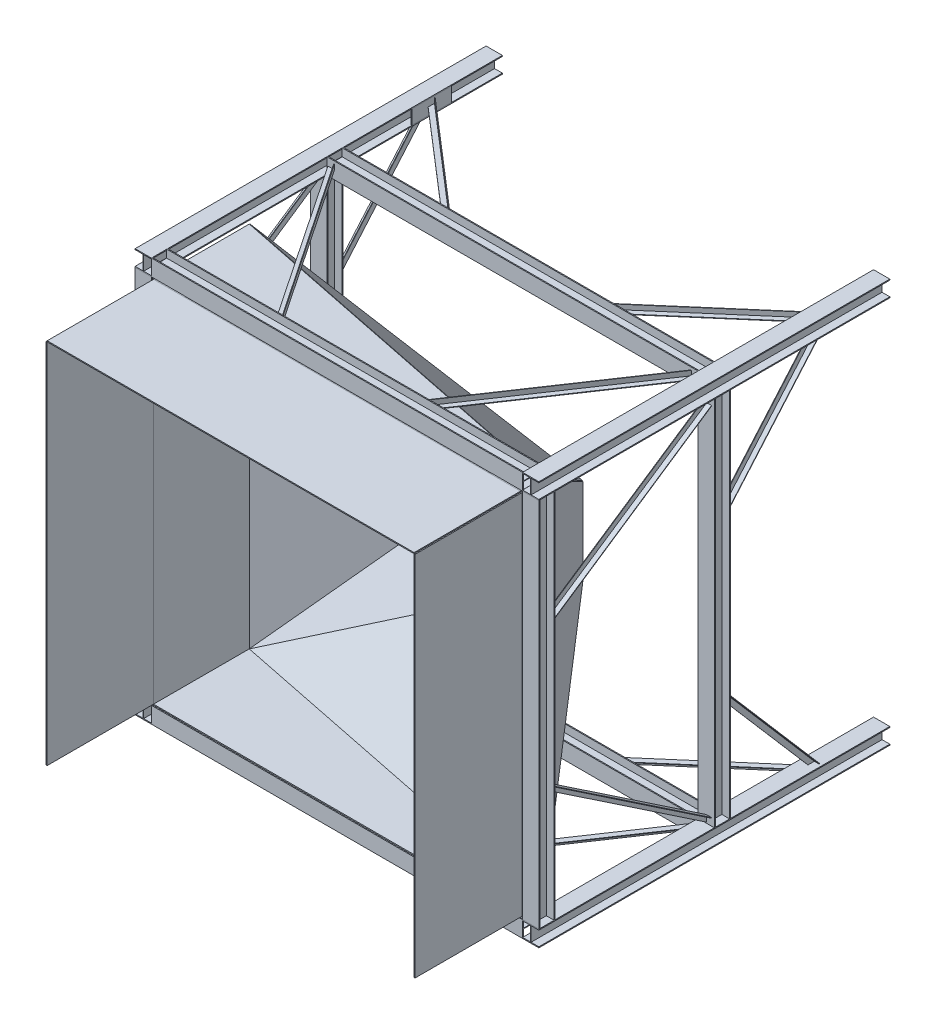
SolidWorks part; units mm, degrees
other "DetailItem1"
other "DetailItem2"
other "DetailItem3"
other "DetailItem4"
other "DetailItem5"
other "DetailItem6"
other "DetailItem7"
other "DetailItem8"
other "DetailItem9"
other "DetailItem10"
other "DetailItem11"
other "DetailItem12"
other "DetailItem13"
other "DetailItem14"
other "DetailItem15"
other "DetailItem16"
other "DetailItem17"
other "DetailItem18"
other "DetailItem19"
other "DetailItem20"
other "DetailItem21"
other "DetailItem22"
other "DetailItem23"
other "DetailItem24"
other "DetailItem25"
other "DetailItem26"
other "DetailItem27"
other "DetailItem28"
other "DetailItem29"
other "DetailItem30"
other "DetailItem31"
other "DetailItem32"
other "DetailItem33"
other "DetailItem34"
other "DetailItem35"
other "DetailItem36"
other "DetailItem37"
other "DetailItem38"
other "DetailItem39"
other "DetailItem40"
other "DetailItem41"
other "DetailItem42"
other "DetailItem43"
other "DetailItem44"
other "DetailItem45"
other "DetailItem46"
other "DetailItem47"
other "DetailItem48"
other "DetailItem49"
other "DetailItem50"
other "DetailItem51"
other "DetailItem52"
other "DetailItem53"
other "DetailItem54"
other "DetailItem55"
other "DetailItem56"
other "DetailItem57"
other "DetailItem58"
other "DetailItem59"
other "DetailItem60"
other "DetailItem61"
other "DetailItem62"
other "DetailItem63"
other "DetailItem64"
other "DetailItem65"
other "DetailItem66"
other "DetailItem67"
other "DetailItem68"
other "DetailItem69"
other "DetailItem70"
other "DetailItem71"
other "DetailItem72"
other "DetailItem73"
other "DetailItem74"
other "DetailItem75"
other "Carpeta de soldadura"
other "Cordón de soldadura1"
other "Soldadura Viga H carga 1650 B"
other "Soldadura Viga H carga 3300 A"
other "Soldadura Viga H carga 3300 B"
other "Soldadura asiento a tolva carga"
other "Soldadura asiento a bastidor carga"
other "Soldadura Viga H fondo 1650 A"
other "Soldadura Viga H fondo 1650 B"
other "Soldadura Viga H fondo 3300 A"
other "Soldadura Viga H fondo 3300 B"
other "Soldadura asiento a tolva fondo"
other "Soldadura asiento a bastidor fondo"
other "Soldadura Viga H izquierda 1650 A"
other "Soldadura Viga H izquierda 1650 B"
other "Soldadura Viga H izquierda 3300 A"
other "Soldadura Viga H izquierda 3300 B"
other "Soldadura asiento a tolva izquierda"
other "Soldadura asiento a bastidor izquierda"
other "Soldadura Viga H derecha 1650 A"
other "Soldadura Viga H derecha 1650 B"
other "Soldadura Viga H derecha 3300 A"
other "Soldadura Viga H derecha 3300 B"
other "Soldadura asiento a tolva derecha"
other "Soldadura asiento a bastidor derecha"
other "Soldadura Angular superior carga A inferior"
other "Soldadura Angular superior carga A superior"
other "Soldadura Angular inferior carga A inferior"
other "Soldadura Angular inferior carga A superior"
other "Soldadura Angular superior carga B inferior"
other "Soldadura Angular superior carga B superior"
other "Soldadura Angular inferior carga B inferior"
other "Soldadura Angular inferior carga B superior"
other "Soldadura Angular superior fondo A inferior"
other "Soldadura Angular superior fondo A superior"
other "Soldadura Angular inferior fondo A inferior"
other "Soldadura Angular inferior fondo A superior"
other "Soldadura Angular superior fondo B inferior"
other "Soldadura Angular superior fondo B superior"
other "Soldadura Angular inferior fondo B inferior"
other "Soldadura Angular inferior fondo B superior"
other "Soldadura Angular superior izquierda A inferior"
other "Soldadura Angular superior izquierda A superior"
other "Soldadura Angular inferior izquierda A inferior"
other "Soldadura Angular inferior izquierda A superior"
other "Soldadura Angular superior izquierda B inferior"
other "Soldadura Angular superior izquierda B superior"
other "Soldadura Angular inferior izquierda B inferior"
other "Soldadura Angular inferior izquierda B superior"
other "Soldadura Angular superior derecha A inferior"
other "Soldadura Angular superior derecha A superior"
other "Soldadura Angular inferior derecha A inferior"
other "Soldadura Angular inferior derecha A superior"
other "Soldadura Angular superior derecha B inferior"
other "Soldadura Angular superior derecha B superior"
other "Soldadura Angular inferior derecha B inferior"
other "Soldadura Angular inferior derecha B superior"
other "Soldadura esquina del collar carga"
other "Soldadura quiebre del embudo carga"
other "Soldadura arista inclinada carga"
other "Soldadura diagonal carga"
other "Soldadura alerón a collar derecha"
other "Soldadura esquina del collar derecha"
other "Soldadura quiebre del embudo derecha"
other "Soldadura arista inclinada derecha"
other "Soldadura alerón a collar fondo"
other "Soldadura esquina del collar fondo"
other "Soldadura quiebre del embudo fondo"
other "Soldadura arista inclinada fondo"
other "Soldadura diagonal fondo"
other "Soldadura alerón a collar izquierda"
other "Soldadura esquina del collar izquierda"
other "Soldadura quiebre del embudo izquierda"
other "Soldadura arista inclinada izquierda"
other "Soldadura esquina alerones derecha"
other "Soldadura esquina alerones izquierda"
material "ASTM A36 Steel"
ref_plane "Front Plane" through (0, 0, 0) normal (0, 0, 1) x (1, 0, 0)
ref_plane "Top Plane" through (0, 0, 0) normal (0, 1, 0) x (1, 0, 0)
ref_plane "Right Plane" through (0, 0, 0) normal (1, 0, 0) x (0, 0, -1)
sketch3d "Referencias 1"
  point P0 (0, 0, 0)
  point P1 (0, -190, 0)
  point P2 (200, 0, 0)
ref_plane "Plano de perfil 1 estructura" through (0, 0, 0) normal (0, 0, 1) x (1, 0, 0)
sketch "Contorno Columna H 1" plane through (0, 0, 0) normal (0, 0, 1) x (1, 0, 0)
  line L0 (-1898, -1898) -> (-1745, -1898)
  line L1 (-1745, -1898) -> (-1745, -1889)
  line L2 (-1745, -1889) -> (-1818.25, -1889)
  line L3 (-1818.25, -1889) -> (-1818.25, -1754)
  line L4 (-1818.25, -1754) -> (-1745, -1754)
  line L5 (-1745, -1754) -> (-1745, -1745)
  line L6 (-1745, -1745) -> (-1898, -1745)
  line L7 (-1898, -1745) -> (-1898, -1754)
  line L8 (-1898, -1754) -> (-1824.75, -1754)
  line L9 (-1824.75, -1754) -> (-1824.75, -1889)
  line L10 (-1824.75, -1889) -> (-1898, -1889)
  line L11 (-1898, -1889) -> (-1898, -1898)
extrude "Columna H 1" add sketch "Contorno Columna H 1" along normal blind 3300 separate body
sketch "Contorno Columna H 2" plane through (0, 0, 0) normal (0, 0, 1) x (1, 0, 0)
  line L0 (-1898, 1745) -> (-1745, 1745)
  line L1 (-1745, 1745) -> (-1745, 1754)
  line L2 (-1745, 1754) -> (-1818.25, 1754)
  line L3 (-1818.25, 1754) -> (-1818.25, 1889)
  line L4 (-1818.25, 1889) -> (-1745, 1889)
  line L5 (-1745, 1889) -> (-1745, 1898)
  line L6 (-1745, 1898) -> (-1898, 1898)
  line L7 (-1898, 1898) -> (-1898, 1889)
  line L8 (-1898, 1889) -> (-1824.75, 1889)
  line L9 (-1824.75, 1889) -> (-1824.75, 1754)
  line L10 (-1824.75, 1754) -> (-1898, 1754)
  line L11 (-1898, 1754) -> (-1898, 1745)
extrude "Columna H 2" add sketch "Contorno Columna H 2" along normal blind 3300 separate body
sketch "Contorno Columna H 3" plane through (0, 0, 0) normal (0, 0, 1) x (1, 0, 0)
  line L0 (1745, -1898) -> (1898, -1898)
  line L1 (1898, -1898) -> (1898, -1889)
  line L2 (1898, -1889) -> (1824.75, -1889)
  line L3 (1824.75, -1889) -> (1824.75, -1754)
  line L4 (1824.75, -1754) -> (1898, -1754)
  line L5 (1898, -1754) -> (1898, -1745)
  line L6 (1898, -1745) -> (1745, -1745)
  line L7 (1745, -1745) -> (1745, -1754)
  line L8 (1745, -1754) -> (1818.25, -1754)
  line L9 (1818.25, -1754) -> (1818.25, -1889)
  line L10 (1818.25, -1889) -> (1745, -1889)
  line L11 (1745, -1889) -> (1745, -1898)
extrude "Columna H 3" add sketch "Contorno Columna H 3" along normal blind 3300 separate body
sketch "Contorno Columna H 4" plane through (0, 0, 0) normal (0, 0, 1) x (1, 0, 0)
  line L0 (1745, 1745) -> (1898, 1745)
  line L1 (1898, 1745) -> (1898, 1754)
  line L2 (1898, 1754) -> (1824.75, 1754)
  line L3 (1824.75, 1754) -> (1824.75, 1889)
  line L4 (1824.75, 1889) -> (1898, 1889)
  line L5 (1898, 1889) -> (1898, 1898)
  line L6 (1898, 1898) -> (1745, 1898)
  line L7 (1745, 1898) -> (1745, 1889)
  line L8 (1745, 1889) -> (1818.25, 1889)
  line L9 (1818.25, 1889) -> (1818.25, 1754)
  line L10 (1818.25, 1754) -> (1745, 1754)
  line L11 (1745, 1754) -> (1745, 1745)
extrude "Columna H 4" add sketch "Contorno Columna H 4" along normal blind 3300 separate body
sketch3d "Referencias 2"
  point P0 (-1745, 0, 0)
  point P1 (-1745, 190, 0)
  point P2 (-1745, 0, 200)
ref_plane "Plano de perfil 2 estructura" through (-1745, 0, 0) normal (1, 0, 0) x (0, 0, -1)
sketch "Contorno Viga H carga 1650" plane through (-1745, 0, 0) normal (1, 0, 0) x (0, 0, -1)
  line L0 (-1497, -1745) -> (-1497, -1898)
  line L1 (-1497, -1898) -> (-1506, -1898)
  line L2 (-1506, -1898) -> (-1506, -1824.75)
  line L3 (-1506, -1824.75) -> (-1641, -1824.75)
  line L4 (-1641, -1824.75) -> (-1641, -1898)
  line L5 (-1641, -1898) -> (-1650, -1898)
  line L6 (-1650, -1898) -> (-1650, -1745)
  line L7 (-1650, -1745) -> (-1641, -1745)
  line L8 (-1641, -1745) -> (-1641, -1818.25)
  line L9 (-1641, -1818.25) -> (-1506, -1818.25)
  line L10 (-1506, -1818.25) -> (-1506, -1745)
  line L11 (-1506, -1745) -> (-1497, -1745)
extrude "Viga H carga 1650" add sketch "Contorno Viga H carga 1650" along normal blind 3490 separate body
sketch "Contorno Viga H carga 3300" plane through (-1745, 0, 0) normal (1, 0, 0) x (0, 0, -1)
  line L0 (-3147, -1745) -> (-3147, -1898)
  line L1 (-3147, -1898) -> (-3156, -1898)
  line L2 (-3156, -1898) -> (-3156, -1824.75)
  line L3 (-3156, -1824.75) -> (-3291, -1824.75)
  line L4 (-3291, -1824.75) -> (-3291, -1898)
  line L5 (-3291, -1898) -> (-3300, -1898)
  line L6 (-3300, -1898) -> (-3300, -1745)
  line L7 (-3300, -1745) -> (-3291, -1745)
  line L8 (-3291, -1745) -> (-3291, -1818.25)
  line L9 (-3291, -1818.25) -> (-3156, -1818.25)
  line L10 (-3156, -1818.25) -> (-3156, -1745)
  line L11 (-3156, -1745) -> (-3147, -1745)
extrude "Viga H carga 3300" add sketch "Contorno Viga H carga 3300" along normal blind 3490 separate body
sketch "Contorno Cierre columna carga A" plane through (-1745, 0, 0) normal (1, 0, 0) x (0, 0, -1)
  line L0 (-480, -1754) -> (-480, -1889)
  line L1 (-480, -1889) -> (-850, -1889)
  line L2 (-850, -1889) -> (-850, -1754)
  line L3 (-850, -1754) -> (-480, -1754)
extrude "Cierre columna carga A" add sketch "Contorno Cierre columna carga A" against normal blind 8 separate body
sketch3d "Referencias 3"
  point P0 (0, -1821.5, 0)
  point P1 (-190, -1821.5, 0)
  point P2 (0, -1821.5, 200)
ref_plane "Plano de perfil 3 estructura" through (0, -1821.5, 0) normal (0, 1, 0) x (1, 0, 0)
sketch "Contorno Ala plana Angular superior carga A" plane through (0, -1821.5, 0) normal (0, 1, 0) x (1, 0, 0)
  line L0 (-1674.8701, -1650) -> (-1735.1299, -1650)
  line L1 (-1735.1299, -1650) -> (-728.1299, -3147)
  line L2 (-728.1299, -3147) -> (-667.8701, -3147)
  line L3 (-667.8701, -3147) -> (-1674.8701, -1650)
extrude "Ala plana Angular superior carga A" add sketch "Contorno Ala plana Angular superior carga A" against normal blind 5 separate body
sketch3d "Referencias 4"
  point P0 (0, -1826.5, 0)
  point P1 (-190, -1826.5, 0)
  point P2 (0, -1826.5, 200)
ref_plane "Plano de perfil 4 estructura" through (0, -1826.5, 0) normal (0, 1, 0) x (1, 0, 0)
sketch "Contorno Retorno Angular superior carga A" plane through (0, -1826.5, 0) normal (0, 1, 0) x (1, 0, 0)
  line L0 (-1674.8701, -1650) -> (-1680.8961, -1650)
  line L1 (-1680.8961, -1650) -> (-673.8961, -3147)
  line L2 (-673.8961, -3147) -> (-667.8701, -3147)
  line L3 (-667.8701, -3147) -> (-1674.8701, -1650)
extrude "Retorno Angular superior carga A" add sketch "Contorno Retorno Angular superior carga A" against normal blind 45 separate body
combine bodies "Angular superior carga A" operation type add bodies to combine 108 109
sketch "Contorno Ala plana Angular inferior carga A" plane through (0, -1821.5, 0) normal (0, 1, 0) x (1, 0, 0)
  line L0 (-1745, -631.991) -> (-1745, -698.009)
  line L1 (-1745, -698.009) -> (-818.2856, -1497)
  line L2 (-818.2856, -1497) -> (-741.7144, -1497)
  line L3 (-741.7144, -1497) -> (-1745, -631.991)
extrude "Ala plana Angular inferior carga A" add sketch "Contorno Ala plana Angular inferior carga A" against normal blind 5 separate body
sketch "Contorno Retorno Angular inferior carga A" plane through (0, -1826.5, 0) normal (0, 1, 0) x (1, 0, 0)
  line L0 (-1745, -631.991) -> (-1745, -638.5928)
  line L1 (-1745, -638.5928) -> (-749.3715, -1497)
  line L2 (-749.3715, -1497) -> (-741.7144, -1497)
  line L3 (-741.7144, -1497) -> (-1745, -631.991)
extrude "Retorno Angular inferior carga A" add sketch "Contorno Retorno Angular inferior carga A" against normal blind 45 separate body
combine bodies "Angular inferior carga A" operation type add bodies to combine 111 112
sketch3d "Referencias 5"
  point P0 (1745, 0, 0)
  point P1 (1745, 190, 0)
  point P2 (1745, 0, 200)
ref_plane "Plano de perfil 5 estructura" through (1745, 0, 0) normal (1, 0, 0) x (0, 0, -1)
sketch "Contorno Cierre columna carga B" plane through (1745, 0, 0) normal (1, 0, 0) x (0, 0, -1)
  line L0 (-480, -1754) -> (-480, -1889)
  line L1 (-480, -1889) -> (-850, -1889)
  line L2 (-850, -1889) -> (-850, -1754)
  line L3 (-850, -1754) -> (-480, -1754)
extrude "Cierre columna carga B" add sketch "Contorno Cierre columna carga B" along normal blind 8 separate body
sketch "Contorno Ala plana Angular superior carga B" plane through (0, -1821.5, 0) normal (0, 1, 0) x (1, 0, 0)
  line L0 (1674.8701, -1650) -> (1735.1299, -1650)
  line L1 (1735.1299, -1650) -> (728.1299, -3147)
  line L2 (728.1299, -3147) -> (667.8701, -3147)
  line L3 (667.8701, -3147) -> (1674.8701, -1650)
extrude "Ala plana Angular superior carga B" add sketch "Contorno Ala plana Angular superior carga B" against normal blind 5 separate body
sketch "Contorno Retorno Angular superior carga B" plane through (0, -1826.5, 0) normal (0, 1, 0) x (1, 0, 0)
  line L0 (1674.8701, -1650) -> (1680.8961, -1650)
  line L1 (1680.8961, -1650) -> (673.8961, -3147)
  line L2 (673.8961, -3147) -> (667.8701, -3147)
  line L3 (667.8701, -3147) -> (1674.8701, -1650)
extrude "Retorno Angular superior carga B" add sketch "Contorno Retorno Angular superior carga B" against normal blind 45 separate body
combine bodies "Angular superior carga B" operation type add bodies to combine 115 116
sketch "Contorno Ala plana Angular inferior carga B" plane through (0, -1821.5, 0) normal (0, 1, 0) x (1, 0, 0)
  line L0 (1745, -631.991) -> (1745, -698.009)
  line L1 (1745, -698.009) -> (818.2856, -1497)
  line L2 (818.2856, -1497) -> (741.7144, -1497)
  line L3 (741.7144, -1497) -> (1745, -631.991)
extrude "Ala plana Angular inferior carga B" add sketch "Contorno Ala plana Angular inferior carga B" against normal blind 5 separate body
sketch "Contorno Retorno Angular inferior carga B" plane through (0, -1826.5, 0) normal (0, 1, 0) x (1, 0, 0)
  line L0 (1745, -631.991) -> (1745, -638.5928)
  line L1 (1745, -638.5928) -> (749.3715, -1497)
  line L2 (749.3715, -1497) -> (741.7144, -1497)
  line L3 (741.7144, -1497) -> (1745, -631.991)
extrude "Retorno Angular inferior carga B" add sketch "Contorno Retorno Angular inferior carga B" against normal blind 45 separate body
combine bodies "Angular inferior carga B" operation type add bodies to combine 118 119
sketch3d "Referencias 6"
  point P0 (0, 0, 3281.475)
  point P1 (0, -190, 3281.475)
  point P2 (200, 0, 3281.475)
ref_plane "Plano de perfil 6 estructura" through (0, 0, 3281.475) normal (0, 0, 1) x (1, 0, 0)
sketch "Contorno Asiento soldado carga" plane through (0, 0, 3281.475) normal (0, 0, 1) x (1, 0, 0)
  line L0 (-1450, -1734.525) -> (1450, -1734.525)
  line L1 (1450, -1734.525) -> (1450, -1818.25)
  line L2 (1450, -1818.25) -> (-1450, -1818.25)
  line L3 (-1450, -1818.25) -> (-1450, -1734.525)
extrude "Asiento soldado carga" add sketch "Contorno Asiento soldado carga" along normal blind 9.525 separate body
sketch "Contorno Viga H fondo 1650" plane through (-1745, 0, 0) normal (1, 0, 0) x (0, 0, -1)
  line L0 (-1497, 1745) -> (-1497, 1898)
  line L1 (-1497, 1898) -> (-1506, 1898)
  line L2 (-1506, 1898) -> (-1506, 1824.75)
  line L3 (-1506, 1824.75) -> (-1641, 1824.75)
  line L4 (-1641, 1824.75) -> (-1641, 1898)
  line L5 (-1641, 1898) -> (-1650, 1898)
  line L6 (-1650, 1898) -> (-1650, 1745)
  line L7 (-1650, 1745) -> (-1641, 1745)
  line L8 (-1641, 1745) -> (-1641, 1818.25)
  line L9 (-1641, 1818.25) -> (-1506, 1818.25)
  line L10 (-1506, 1818.25) -> (-1506, 1745)
  line L11 (-1506, 1745) -> (-1497, 1745)
extrude "Viga H fondo 1650" add sketch "Contorno Viga H fondo 1650" along normal blind 3490 separate body
sketch "Contorno Viga H fondo 3300" plane through (-1745, 0, 0) normal (1, 0, 0) x (0, 0, -1)
  line L0 (-3147, 1745) -> (-3147, 1898)
  line L1 (-3147, 1898) -> (-3156, 1898)
  line L2 (-3156, 1898) -> (-3156, 1824.75)
  line L3 (-3156, 1824.75) -> (-3291, 1824.75)
  line L4 (-3291, 1824.75) -> (-3291, 1898)
  line L5 (-3291, 1898) -> (-3300, 1898)
  line L6 (-3300, 1898) -> (-3300, 1745)
  line L7 (-3300, 1745) -> (-3291, 1745)
  line L8 (-3291, 1745) -> (-3291, 1818.25)
  line L9 (-3291, 1818.25) -> (-3156, 1818.25)
  line L10 (-3156, 1818.25) -> (-3156, 1745)
  line L11 (-3156, 1745) -> (-3147, 1745)
extrude "Viga H fondo 3300" add sketch "Contorno Viga H fondo 3300" along normal blind 3490 separate body
sketch "Contorno Cierre columna fondo A" plane through (-1745, 0, 0) normal (1, 0, 0) x (0, 0, -1)
  line L0 (-480, 1754) -> (-480, 1889)
  line L1 (-480, 1889) -> (-850, 1889)
  line L2 (-850, 1889) -> (-850, 1754)
  line L3 (-850, 1754) -> (-480, 1754)
extrude "Cierre columna fondo A" add sketch "Contorno Cierre columna fondo A" against normal blind 8 separate body
sketch3d "Referencias 7"
  point P0 (0, 1821.5, 0)
  point P1 (-190, 1821.5, 0)
  point P2 (0, 1821.5, 200)
ref_plane "Plano de perfil 7 estructura" through (0, 1821.5, 0) normal (0, 1, 0) x (1, 0, 0)
sketch "Contorno Ala plana Angular superior fondo A" plane through (0, 1821.5, 0) normal (0, 1, 0) x (1, 0, 0)
  line L0 (-1674.8701, -1650) -> (-1735.1299, -1650)
  line L1 (-1735.1299, -1650) -> (-728.1299, -3147)
  line L2 (-728.1299, -3147) -> (-667.8701, -3147)
  line L3 (-667.8701, -3147) -> (-1674.8701, -1650)
extrude "Ala plana Angular superior fondo A" add sketch "Contorno Ala plana Angular superior fondo A" along normal blind 5 separate body
sketch3d "Referencias 8"
  point P0 (0, 1826.5, 0)
  point P1 (-190, 1826.5, 0)
  point P2 (0, 1826.5, 200)
ref_plane "Plano de perfil 8 estructura" through (0, 1826.5, 0) normal (0, 1, 0) x (1, 0, 0)
sketch "Contorno Retorno Angular superior fondo A" plane through (0, 1826.5, 0) normal (0, 1, 0) x (1, 0, 0)
  line L0 (-1674.8701, -1650) -> (-1680.8961, -1650)
  line L1 (-1680.8961, -1650) -> (-673.8961, -3147)
  line L2 (-673.8961, -3147) -> (-667.8701, -3147)
  line L3 (-667.8701, -3147) -> (-1674.8701, -1650)
extrude "Retorno Angular superior fondo A" add sketch "Contorno Retorno Angular superior fondo A" along normal blind 45 separate body
combine bodies "Angular superior fondo A" operation type add bodies to combine 125 126
sketch "Contorno Ala plana Angular inferior fondo A" plane through (0, 1821.5, 0) normal (0, 1, 0) x (1, 0, 0)
  line L0 (-1745, -631.991) -> (-1745, -698.009)
  line L1 (-1745, -698.009) -> (-818.2856, -1497)
  line L2 (-818.2856, -1497) -> (-741.7144, -1497)
  line L3 (-741.7144, -1497) -> (-1745, -631.991)
extrude "Ala plana Angular inferior fondo A" add sketch "Contorno Ala plana Angular inferior fondo A" along normal blind 5 separate body
sketch "Contorno Retorno Angular inferior fondo A" plane through (0, 1826.5, 0) normal (0, 1, 0) x (1, 0, 0)
  line L0 (-1745, -631.991) -> (-1745, -638.5928)
  line L1 (-1745, -638.5928) -> (-749.3715, -1497)
  line L2 (-749.3715, -1497) -> (-741.7144, -1497)
  line L3 (-741.7144, -1497) -> (-1745, -631.991)
extrude "Retorno Angular inferior fondo A" add sketch "Contorno Retorno Angular inferior fondo A" along normal blind 45 separate body
combine bodies "Angular inferior fondo A" operation type add bodies to combine 128 129
sketch "Contorno Cierre columna fondo B" plane through (1745, 0, 0) normal (1, 0, 0) x (0, 0, -1)
  line L0 (-480, 1754) -> (-480, 1889)
  line L1 (-480, 1889) -> (-850, 1889)
  line L2 (-850, 1889) -> (-850, 1754)
  line L3 (-850, 1754) -> (-480, 1754)
extrude "Cierre columna fondo B" add sketch "Contorno Cierre columna fondo B" along normal blind 8 separate body
sketch "Contorno Ala plana Angular superior fondo B" plane through (0, 1821.5, 0) normal (0, 1, 0) x (1, 0, 0)
  line L0 (1674.8701, -1650) -> (1735.1299, -1650)
  line L1 (1735.1299, -1650) -> (728.1299, -3147)
  line L2 (728.1299, -3147) -> (667.8701, -3147)
  line L3 (667.8701, -3147) -> (1674.8701, -1650)
extrude "Ala plana Angular superior fondo B" add sketch "Contorno Ala plana Angular superior fondo B" along normal blind 5 separate body
sketch "Contorno Retorno Angular superior fondo B" plane through (0, 1826.5, 0) normal (0, 1, 0) x (1, 0, 0)
  line L0 (1674.8701, -1650) -> (1680.8961, -1650)
  line L1 (1680.8961, -1650) -> (673.8961, -3147)
  line L2 (673.8961, -3147) -> (667.8701, -3147)
  line L3 (667.8701, -3147) -> (1674.8701, -1650)
extrude "Retorno Angular superior fondo B" add sketch "Contorno Retorno Angular superior fondo B" along normal blind 45 separate body
combine bodies "Angular superior fondo B" operation type add bodies to combine 132 133
sketch "Contorno Ala plana Angular inferior fondo B" plane through (0, 1821.5, 0) normal (0, 1, 0) x (1, 0, 0)
  line L0 (1745, -631.991) -> (1745, -698.009)
  line L1 (1745, -698.009) -> (818.2856, -1497)
  line L2 (818.2856, -1497) -> (741.7144, -1497)
  line L3 (741.7144, -1497) -> (1745, -631.991)
extrude "Ala plana Angular inferior fondo B" add sketch "Contorno Ala plana Angular inferior fondo B" along normal blind 5 separate body
sketch "Contorno Retorno Angular inferior fondo B" plane through (0, 1826.5, 0) normal (0, 1, 0) x (1, 0, 0)
  line L0 (1745, -631.991) -> (1745, -638.5928)
  line L1 (1745, -638.5928) -> (749.3715, -1497)
  line L2 (749.3715, -1497) -> (741.7144, -1497)
  line L3 (741.7144, -1497) -> (1745, -631.991)
extrude "Retorno Angular inferior fondo B" add sketch "Contorno Retorno Angular inferior fondo B" along normal blind 45 separate body
combine bodies "Angular inferior fondo B" operation type add bodies to combine 135 136
sketch "Contorno Asiento soldado fondo" plane through (0, 0, 3281.475) normal (0, 0, 1) x (1, 0, 0)
  line L0 (-1450, 1734.525) -> (1450, 1734.525)
  line L1 (1450, 1734.525) -> (1450, 1818.25)
  line L2 (1450, 1818.25) -> (-1450, 1818.25)
  line L3 (-1450, 1818.25) -> (-1450, 1734.525)
extrude "Asiento soldado fondo" add sketch "Contorno Asiento soldado fondo" along normal blind 9.525 separate body
sketch3d "Referencias 9"
  point P0 (0, -1745, 0)
  point P1 (-190, -1745, 0)
  point P2 (0, -1745, 200)
ref_plane "Plano de perfil 9 estructura" through (0, -1745, 0) normal (0, 1, 0) x (1, 0, 0)
sketch "Contorno Viga H izquierda 1650" plane through (0, -1745, 0) normal (0, 1, 0) x (1, 0, 0)
  line L0 (-1745, -1497) -> (-1898, -1497)
  line L1 (-1898, -1497) -> (-1898, -1506)
  line L2 (-1898, -1506) -> (-1824.75, -1506)
  line L3 (-1824.75, -1506) -> (-1824.75, -1641)
  line L4 (-1824.75, -1641) -> (-1898, -1641)
  line L5 (-1898, -1641) -> (-1898, -1650)
  line L6 (-1898, -1650) -> (-1745, -1650)
  line L7 (-1745, -1650) -> (-1745, -1641)
  line L8 (-1745, -1641) -> (-1818.25, -1641)
  line L9 (-1818.25, -1641) -> (-1818.25, -1506)
  line L10 (-1818.25, -1506) -> (-1745, -1506)
  line L11 (-1745, -1506) -> (-1745, -1497)
extrude "Viga H izquierda 1650" add sketch "Contorno Viga H izquierda 1650" along normal blind 3490 separate body
sketch "Contorno Viga H izquierda 3300" plane through (0, -1745, 0) normal (0, 1, 0) x (1, 0, 0)
  line L0 (-1745, -3147) -> (-1898, -3147)
  line L1 (-1898, -3147) -> (-1898, -3156)
  line L2 (-1898, -3156) -> (-1824.75, -3156)
  line L3 (-1824.75, -3156) -> (-1824.75, -3291)
  line L4 (-1824.75, -3291) -> (-1898, -3291)
  line L5 (-1898, -3291) -> (-1898, -3300)
  line L6 (-1898, -3300) -> (-1745, -3300)
  line L7 (-1745, -3300) -> (-1745, -3291)
  line L8 (-1745, -3291) -> (-1818.25, -3291)
  line L9 (-1818.25, -3291) -> (-1818.25, -3156)
  line L10 (-1818.25, -3156) -> (-1745, -3156)
  line L11 (-1745, -3156) -> (-1745, -3147)
extrude "Viga H izquierda 3300" add sketch "Contorno Viga H izquierda 3300" along normal blind 3490 separate body
sketch3d "Referencias 10"
  point P0 (-1821.5, 0, 0)
  point P1 (-1821.5, 190, 0)
  point P2 (-1821.5, 0, 200)
ref_plane "Plano de perfil 10 estructura" through (-1821.5, 0, 0) normal (1, 0, 0) x (0, 0, -1)
sketch "Contorno Ala plana Angular superior izquierda A" plane through (-1821.5, 0, 0) normal (1, 0, 0) x (0, 0, -1)
  line L0 (-1650, -1674.8701) -> (-1650, -1735.1299)
  line L1 (-1650, -1735.1299) -> (-3147, -728.1299)
  line L2 (-3147, -728.1299) -> (-3147, -667.8701)
  line L3 (-3147, -667.8701) -> (-1650, -1674.8701)
extrude "Ala plana Angular superior izquierda A" add sketch "Contorno Ala plana Angular superior izquierda A" against normal blind 5 separate body
sketch3d "Referencias 11"
  point P0 (-1826.5, 0, 0)
  point P1 (-1826.5, 190, 0)
  point P2 (-1826.5, 0, 200)
ref_plane "Plano de perfil 11 estructura" through (-1826.5, 0, 0) normal (1, 0, 0) x (0, 0, -1)
sketch "Contorno Retorno Angular superior izquierda A" plane through (-1826.5, 0, 0) normal (1, 0, 0) x (0, 0, -1)
  line L0 (-1650, -1674.8701) -> (-1650, -1680.8961)
  line L1 (-1650, -1680.8961) -> (-3147, -673.8961)
  line L2 (-3147, -673.8961) -> (-3147, -667.8701)
  line L3 (-3147, -667.8701) -> (-1650, -1674.8701)
extrude "Retorno Angular superior izquierda A" add sketch "Contorno Retorno Angular superior izquierda A" against normal blind 45 separate body
combine bodies "Angular superior izquierda A" operation type add bodies to combine 141 142
sketch "Contorno Ala plana Angular inferior izquierda A" plane through (-1821.5, 0, 0) normal (1, 0, 0) x (0, 0, -1)
  line L0 (-631.991, -1745) -> (-698.009, -1745)
  line L1 (-698.009, -1745) -> (-1497, -818.2856)
  line L2 (-1497, -818.2856) -> (-1497, -741.7144)
  line L3 (-1497, -741.7144) -> (-631.991, -1745)
extrude "Ala plana Angular inferior izquierda A" add sketch "Contorno Ala plana Angular inferior izquierda A" against normal blind 5 separate body
sketch "Contorno Retorno Angular inferior izquierda A" plane through (-1826.5, 0, 0) normal (1, 0, 0) x (0, 0, -1)
  line L0 (-631.991, -1745) -> (-638.5928, -1745)
  line L1 (-638.5928, -1745) -> (-1497, -749.3715)
  line L2 (-1497, -749.3715) -> (-1497, -741.7144)
  line L3 (-1497, -741.7144) -> (-631.991, -1745)
extrude "Retorno Angular inferior izquierda A" add sketch "Contorno Retorno Angular inferior izquierda A" against normal blind 45 separate body
combine bodies "Angular inferior izquierda A" operation type add bodies to combine 144 145
sketch "Contorno Ala plana Angular superior izquierda B" plane through (-1821.5, 0, 0) normal (1, 0, 0) x (0, 0, -1)
  line L0 (-1650, 1674.8701) -> (-1650, 1735.1299)
  line L1 (-1650, 1735.1299) -> (-3147, 728.1299)
  line L2 (-3147, 728.1299) -> (-3147, 667.8701)
  line L3 (-3147, 667.8701) -> (-1650, 1674.8701)
extrude "Ala plana Angular superior izquierda B" add sketch "Contorno Ala plana Angular superior izquierda B" against normal blind 5 separate body
sketch "Contorno Retorno Angular superior izquierda B" plane through (-1826.5, 0, 0) normal (1, 0, 0) x (0, 0, -1)
  line L0 (-1650, 1674.8701) -> (-1650, 1680.8961)
  line L1 (-1650, 1680.8961) -> (-3147, 673.8961)
  line L2 (-3147, 673.8961) -> (-3147, 667.8701)
  line L3 (-3147, 667.8701) -> (-1650, 1674.8701)
extrude "Retorno Angular superior izquierda B" add sketch "Contorno Retorno Angular superior izquierda B" against normal blind 45 separate body
combine bodies "Angular superior izquierda B" operation type add bodies to combine 147 148
sketch "Contorno Ala plana Angular inferior izquierda B" plane through (-1821.5, 0, 0) normal (1, 0, 0) x (0, 0, -1)
  line L0 (-631.991, 1745) -> (-698.009, 1745)
  line L1 (-698.009, 1745) -> (-1497, 818.2856)
  line L2 (-1497, 818.2856) -> (-1497, 741.7144)
  line L3 (-1497, 741.7144) -> (-631.991, 1745)
extrude "Ala plana Angular inferior izquierda B" add sketch "Contorno Ala plana Angular inferior izquierda B" against normal blind 5 separate body
sketch "Contorno Retorno Angular inferior izquierda B" plane through (-1826.5, 0, 0) normal (1, 0, 0) x (0, 0, -1)
  line L0 (-631.991, 1745) -> (-638.5928, 1745)
  line L1 (-638.5928, 1745) -> (-1497, 749.3715)
  line L2 (-1497, 749.3715) -> (-1497, 741.7144)
  line L3 (-1497, 741.7144) -> (-631.991, 1745)
extrude "Retorno Angular inferior izquierda B" add sketch "Contorno Retorno Angular inferior izquierda B" against normal blind 45 separate body
combine bodies "Angular inferior izquierda B" operation type add bodies to combine 150 151
sketch "Contorno Asiento soldado izquierda" plane through (0, 0, 3281.475) normal (0, 0, 1) x (1, 0, 0)
  line L0 (-1734.525, -1450) -> (-1734.525, 1450)
  line L1 (-1734.525, 1450) -> (-1818.25, 1450)
  line L2 (-1818.25, 1450) -> (-1818.25, -1450)
  line L3 (-1818.25, -1450) -> (-1734.525, -1450)
extrude "Asiento soldado izquierda" add sketch "Contorno Asiento soldado izquierda" along normal blind 9.525 separate body
sketch "Contorno Viga H derecha 1650" plane through (0, -1745, 0) normal (0, 1, 0) x (1, 0, 0)
  line L0 (1745, -1497) -> (1898, -1497)
  line L1 (1898, -1497) -> (1898, -1506)
  line L2 (1898, -1506) -> (1824.75, -1506)
  line L3 (1824.75, -1506) -> (1824.75, -1641)
  line L4 (1824.75, -1641) -> (1898, -1641)
  line L5 (1898, -1641) -> (1898, -1650)
  line L6 (1898, -1650) -> (1745, -1650)
  line L7 (1745, -1650) -> (1745, -1641)
  line L8 (1745, -1641) -> (1818.25, -1641)
  line L9 (1818.25, -1641) -> (1818.25, -1506)
  line L10 (1818.25, -1506) -> (1745, -1506)
  line L11 (1745, -1506) -> (1745, -1497)
extrude "Viga H derecha 1650" add sketch "Contorno Viga H derecha 1650" along normal blind 3490 separate body
sketch "Contorno Viga H derecha 3300" plane through (0, -1745, 0) normal (0, 1, 0) x (1, 0, 0)
  line L0 (1745, -3147) -> (1898, -3147)
  line L1 (1898, -3147) -> (1898, -3156)
  line L2 (1898, -3156) -> (1824.75, -3156)
  line L3 (1824.75, -3156) -> (1824.75, -3291)
  line L4 (1824.75, -3291) -> (1898, -3291)
  line L5 (1898, -3291) -> (1898, -3300)
  line L6 (1898, -3300) -> (1745, -3300)
  line L7 (1745, -3300) -> (1745, -3291)
  line L8 (1745, -3291) -> (1818.25, -3291)
  line L9 (1818.25, -3291) -> (1818.25, -3156)
  line L10 (1818.25, -3156) -> (1745, -3156)
  line L11 (1745, -3156) -> (1745, -3147)
extrude "Viga H derecha 3300" add sketch "Contorno Viga H derecha 3300" along normal blind 3490 separate body
sketch3d "Referencias 12"
  point P0 (1821.5, 0, 0)
  point P1 (1821.5, 190, 0)
  point P2 (1821.5, 0, 200)
ref_plane "Plano de perfil 12 estructura" through (1821.5, 0, 0) normal (1, 0, 0) x (0, 0, -1)
sketch "Contorno Ala plana Angular superior derecha A" plane through (1821.5, 0, 0) normal (1, 0, 0) x (0, 0, -1)
  line L0 (-1650, -1674.8701) -> (-1650, -1735.1299)
  line L1 (-1650, -1735.1299) -> (-3147, -728.1299)
  line L2 (-3147, -728.1299) -> (-3147, -667.8701)
  line L3 (-3147, -667.8701) -> (-1650, -1674.8701)
extrude "Ala plana Angular superior derecha A" add sketch "Contorno Ala plana Angular superior derecha A" along normal blind 5 separate body
sketch3d "Referencias 13"
  point P0 (1826.5, 0, 0)
  point P1 (1826.5, 190, 0)
  point P2 (1826.5, 0, 200)
ref_plane "Plano de perfil 13 estructura" through (1826.5, 0, 0) normal (1, 0, 0) x (0, 0, -1)
sketch "Contorno Retorno Angular superior derecha A" plane through (1826.5, 0, 0) normal (1, 0, 0) x (0, 0, -1)
  line L0 (-1650, -1674.8701) -> (-1650, -1680.8961)
  line L1 (-1650, -1680.8961) -> (-3147, -673.8961)
  line L2 (-3147, -673.8961) -> (-3147, -667.8701)
  line L3 (-3147, -667.8701) -> (-1650, -1674.8701)
extrude "Retorno Angular superior derecha A" add sketch "Contorno Retorno Angular superior derecha A" along normal blind 45 separate body
combine bodies "Angular superior derecha A" operation type add bodies to combine 156 157
sketch "Contorno Ala plana Angular inferior derecha A" plane through (1821.5, 0, 0) normal (1, 0, 0) x (0, 0, -1)
  line L0 (-631.991, -1745) -> (-698.009, -1745)
  line L1 (-698.009, -1745) -> (-1497, -818.2856)
  line L2 (-1497, -818.2856) -> (-1497, -741.7144)
  line L3 (-1497, -741.7144) -> (-631.991, -1745)
extrude "Ala plana Angular inferior derecha A" add sketch "Contorno Ala plana Angular inferior derecha A" along normal blind 5 separate body
sketch "Contorno Retorno Angular inferior derecha A" plane through (1826.5, 0, 0) normal (1, 0, 0) x (0, 0, -1)
  line L0 (-631.991, -1745) -> (-638.5928, -1745)
  line L1 (-638.5928, -1745) -> (-1497, -749.3715)
  line L2 (-1497, -749.3715) -> (-1497, -741.7144)
  line L3 (-1497, -741.7144) -> (-631.991, -1745)
extrude "Retorno Angular inferior derecha A" add sketch "Contorno Retorno Angular inferior derecha A" along normal blind 45 separate body
combine bodies "Angular inferior derecha A" operation type add bodies to combine 159 160
sketch "Contorno Ala plana Angular superior derecha B" plane through (1821.5, 0, 0) normal (1, 0, 0) x (0, 0, -1)
  line L0 (-1650, 1674.8701) -> (-1650, 1735.1299)
  line L1 (-1650, 1735.1299) -> (-3147, 728.1299)
  line L2 (-3147, 728.1299) -> (-3147, 667.8701)
  line L3 (-3147, 667.8701) -> (-1650, 1674.8701)
extrude "Ala plana Angular superior derecha B" add sketch "Contorno Ala plana Angular superior derecha B" along normal blind 5 separate body
sketch "Contorno Retorno Angular superior derecha B" plane through (1826.5, 0, 0) normal (1, 0, 0) x (0, 0, -1)
  line L0 (-1650, 1674.8701) -> (-1650, 1680.8961)
  line L1 (-1650, 1680.8961) -> (-3147, 673.8961)
  line L2 (-3147, 673.8961) -> (-3147, 667.8701)
  line L3 (-3147, 667.8701) -> (-1650, 1674.8701)
extrude "Retorno Angular superior derecha B" add sketch "Contorno Retorno Angular superior derecha B" along normal blind 45 separate body
combine bodies "Angular superior derecha B" operation type add bodies to combine 162 163
sketch "Contorno Ala plana Angular inferior derecha B" plane through (1821.5, 0, 0) normal (1, 0, 0) x (0, 0, -1)
  line L0 (-631.991, 1745) -> (-698.009, 1745)
  line L1 (-698.009, 1745) -> (-1497, 818.2856)
  line L2 (-1497, 818.2856) -> (-1497, 741.7144)
  line L3 (-1497, 741.7144) -> (-631.991, 1745)
extrude "Ala plana Angular inferior derecha B" add sketch "Contorno Ala plana Angular inferior derecha B" along normal blind 5 separate body
sketch "Contorno Retorno Angular inferior derecha B" plane through (1826.5, 0, 0) normal (1, 0, 0) x (0, 0, -1)
  line L0 (-631.991, 1745) -> (-638.5928, 1745)
  line L1 (-638.5928, 1745) -> (-1497, 749.3715)
  line L2 (-1497, 749.3715) -> (-1497, 741.7144)
  line L3 (-1497, 741.7144) -> (-631.991, 1745)
extrude "Retorno Angular inferior derecha B" add sketch "Contorno Retorno Angular inferior derecha B" along normal blind 45 separate body
combine bodies "Angular inferior derecha B" operation type add bodies to combine 165 166
sketch "Contorno Asiento soldado derecha" plane through (0, 0, 3281.475) normal (0, 0, 1) x (1, 0, 0)
  line L0 (1734.525, -1450) -> (1734.525, 1450)
  line L1 (1734.525, 1450) -> (1818.25, 1450)
  line L2 (1818.25, 1450) -> (1818.25, -1450)
  line L3 (1818.25, -1450) -> (1734.525, -1450)
extrude "Asiento soldado derecha" add sketch "Contorno Asiento soldado derecha" along normal blind 9.525 separate body
sketch3d "Junta Viga H carga 1650 A"
  line L0 (-1745, -1745, 1650) -> (-1745, -1898, 1650)
sketch3d "Junta Viga H carga 1650 B"
  line L0 (1745, -1745, 1650) -> (1745, -1898, 1650)
sketch3d "Junta Viga H carga 3300 A"
  line L0 (-1745, -1745, 3300) -> (-1745, -1898, 3300)
sketch3d "Junta Viga H carga 3300 B"
  line L0 (1745, -1745, 3300) -> (1745, -1898, 3300)
sketch3d "Junta Angular superior carga A inferior"
  line L0 (-1674.8701, -1821.5, 1650) -> (-1735.1299, -1821.5, 1650)
sketch3d "Junta Angular superior carga A superior"
  line L0 (-667.8701, -1821.5, 3147) -> (-728.1299, -1821.5, 3147)
sketch3d "Junta Angular inferior carga A inferior"
  line L0 (-1745, -1821.5, 631.991) -> (-1745, -1821.5, 698.009)
sketch3d "Junta Angular inferior carga A superior"
  line L0 (-741.7144, -1821.5, 1497) -> (-818.2856, -1821.5, 1497)
sketch3d "Junta Angular superior carga B inferior"
  line L0 (1674.8701, -1821.5, 1650) -> (1735.1299, -1821.5, 1650)
sketch3d "Junta Angular superior carga B superior"
  line L0 (667.8701, -1821.5, 3147) -> (728.1299, -1821.5, 3147)
sketch3d "Junta Angular inferior carga B inferior"
  line L0 (1745, -1821.5, 631.991) -> (1745, -1821.5, 698.009)
sketch3d "Junta Angular inferior carga B superior"
  line L0 (741.7144, -1821.5, 1497) -> (818.2856, -1821.5, 1497)
sketch3d "Junta asiento a tolva carga"
  line L0 (-1450, -1734.525, 3281.475) -> (1450, -1734.525, 3281.475)
sketch3d "Junta asiento a bastidor carga"
  line L0 (-1450, -1745, 3291) -> (1450, -1745, 3291)
sketch3d "Junta Viga H fondo 1650 A"
  line L0 (-1745, 1745, 1650) -> (-1745, 1898, 1650)
sketch3d "Junta Viga H fondo 1650 B"
  line L0 (1745, 1745, 1650) -> (1745, 1898, 1650)
sketch3d "Junta Viga H fondo 3300 A"
  line L0 (-1745, 1745, 3300) -> (-1745, 1898, 3300)
sketch3d "Junta Viga H fondo 3300 B"
  line L0 (1745, 1745, 3300) -> (1745, 1898, 3300)
sketch3d "Junta Angular superior fondo A inferior"
  line L0 (-1674.8701, 1821.5, 1650) -> (-1735.1299, 1821.5, 1650)
sketch3d "Junta Angular superior fondo A superior"
  line L0 (-667.8701, 1821.5, 3147) -> (-728.1299, 1821.5, 3147)
sketch3d "Junta Angular inferior fondo A inferior"
  line L0 (-1745, 1821.5, 631.991) -> (-1745, 1821.5, 698.009)
sketch3d "Junta Angular inferior fondo A superior"
  line L0 (-741.7144, 1821.5, 1497) -> (-818.2856, 1821.5, 1497)
sketch3d "Junta Angular superior fondo B inferior"
  line L0 (1674.8701, 1821.5, 1650) -> (1735.1299, 1821.5, 1650)
sketch3d "Junta Angular superior fondo B superior"
  line L0 (667.8701, 1821.5, 3147) -> (728.1299, 1821.5, 3147)
sketch3d "Junta Angular inferior fondo B inferior"
  line L0 (1745, 1821.5, 631.991) -> (1745, 1821.5, 698.009)
sketch3d "Junta Angular inferior fondo B superior"
  line L0 (741.7144, 1821.5, 1497) -> (818.2856, 1821.5, 1497)
sketch3d "Junta asiento a tolva fondo"
  line L0 (-1450, 1734.525, 3281.475) -> (1450, 1734.525, 3281.475)
sketch3d "Junta asiento a bastidor fondo"
  line L0 (-1450, 1745, 3291) -> (1450, 1745, 3291)
sketch3d "Junta Viga H izquierda 1650 A"
  line L0 (-1745, -1745, 1650) -> (-1898, -1745, 1650)
sketch3d "Junta Viga H izquierda 1650 B"
  line L0 (-1745, 1745, 1650) -> (-1898, 1745, 1650)
sketch3d "Junta Viga H izquierda 3300 A"
  line L0 (-1745, -1745, 3300) -> (-1898, -1745, 3300)
sketch3d "Junta Viga H izquierda 3300 B"
  line L0 (-1745, 1745, 3300) -> (-1898, 1745, 3300)
sketch3d "Junta Angular superior izquierda A inferior"
  line L0 (-1821.5, -1674.8701, 1650) -> (-1821.5, -1735.1299, 1650)
sketch3d "Junta Angular superior izquierda A superior"
  line L0 (-1821.5, -667.8701, 3147) -> (-1821.5, -728.1299, 3147)
sketch3d "Junta Angular inferior izquierda A inferior"
  line L0 (-1821.5, -1745, 631.991) -> (-1821.5, -1745, 698.009)
sketch3d "Junta Angular inferior izquierda A superior"
  line L0 (-1821.5, -741.7144, 1497) -> (-1821.5, -818.2856, 1497)
sketch3d "Junta Angular superior izquierda B inferior"
  line L0 (-1821.5, 1674.8701, 1650) -> (-1821.5, 1735.1299, 1650)
sketch3d "Junta Angular superior izquierda B superior"
  line L0 (-1821.5, 667.8701, 3147) -> (-1821.5, 728.1299, 3147)
sketch3d "Junta Angular inferior izquierda B inferior"
  line L0 (-1821.5, 1745, 631.991) -> (-1821.5, 1745, 698.009)
sketch3d "Junta Angular inferior izquierda B superior"
  line L0 (-1821.5, 741.7144, 1497) -> (-1821.5, 818.2856, 1497)
sketch3d "Junta asiento a tolva izquierda"
  line L0 (-1734.525, -1450, 3281.475) -> (-1734.525, 1450, 3281.475)
sketch3d "Junta asiento a bastidor izquierda"
  line L0 (-1745, -1450, 3291) -> (-1745, 1450, 3291)
sketch3d "Junta Viga H derecha 1650 A"
  line L0 (1745, -1745, 1650) -> (1898, -1745, 1650)
sketch3d "Junta Viga H derecha 1650 B"
  line L0 (1745, 1745, 1650) -> (1898, 1745, 1650)
sketch3d "Junta Viga H derecha 3300 A"
  line L0 (1745, -1745, 3300) -> (1898, -1745, 3300)
sketch3d "Junta Viga H derecha 3300 B"
  line L0 (1745, 1745, 3300) -> (1898, 1745, 3300)
sketch3d "Junta Angular superior derecha A inferior"
  line L0 (1821.5, -1674.8701, 1650) -> (1821.5, -1735.1299, 1650)
sketch3d "Junta Angular superior derecha A superior"
  line L0 (1821.5, -667.8701, 3147) -> (1821.5, -728.1299, 3147)
sketch3d "Junta Angular inferior derecha A inferior"
  line L0 (1821.5, -1745, 631.991) -> (1821.5, -1745, 698.009)
sketch3d "Junta Angular inferior derecha A superior"
  line L0 (1821.5, -741.7144, 1497) -> (1821.5, -818.2856, 1497)
sketch3d "Junta Angular superior derecha B inferior"
  line L0 (1821.5, 1674.8701, 1650) -> (1821.5, 1735.1299, 1650)
sketch3d "Junta Angular superior derecha B superior"
  line L0 (1821.5, 667.8701, 3147) -> (1821.5, 728.1299, 3147)
sketch3d "Junta Angular inferior derecha B inferior"
  line L0 (1821.5, 1745, 631.991) -> (1821.5, 1745, 698.009)
sketch3d "Junta Angular inferior derecha B superior"
  line L0 (1821.5, 741.7144, 1497) -> (1821.5, 818.2856, 1497)
sketch3d "Junta asiento a tolva derecha"
  line L0 (1734.525, -1450, 3281.475) -> (1734.525, 1450, 3281.475)
sketch3d "Junta asiento a bastidor derecha"
  line L0 (1745, -1450, 3291) -> (1745, 1450, 3291)
sketch3d "Croquis3D1"
  point P0 (0, -1725, 0)
  point P1 (-190, -1725, 0)
  point P2 (0, -1725, 200)
ref_plane "Plano de perfil 1 tolva" through (0, -1725, 0) normal (0, 1, 0) x (1, 0, 0)
sketch "Contorno Collar carga" plane through (0, -1725, 0) normal (0, 1, 0) x (1, 0, 0)
  line L0 (-1725, -3300) -> (1725, -3300)
  line L1 (1725, -3300) -> (1725, -3100)
  line L2 (1725, -3100) -> (-1725, -2400)
  line L3 (-1725, -2400) -> (-1725, -3300)
extrude "Collar carga" add sketch "Contorno Collar carga" against normal blind 9.525 separate body
sketch3d "Croquis3D2"
  point P0 (-113.1477, 535.2405, 557.6566)
  point P1 (72.7441, 574.5373, 557.6566)
  point P2 (-83.6193, 395.5574, 697.7162)
ref_plane "Plano de perfil 2 tolva" through (-113.1477, 535.2405, 557.6566) normal (0.1448, -0.6852, -0.7139) x (-0.9895, -0.1003, -0.1045)
sketch "Contorno Embudo carga paño superior" plane through (-113.1477, 535.2405, 557.6566) normal (0.1448, -0.6852, -0.7139) x (-0.9895, -0.1003, -0.1045)
  line L0 (1629.0301, -2906.4145) -> (-1857.7372, -3391.135)
  line L1 (-1857.7372, -3391.135) -> (-720.7479, -1396.516)
  line L2 (-720.7479, -1396.516) -> (1629.0301, -2906.4145)
extrude "Embudo carga paño superior" add sketch "Contorno Embudo carga paño superior" along normal blind 9.525 separate body
sketch3d "Croquis3D3"
  point P0 (0, 601.0957, 995.5648)
  point P1 (0, 438.4435, 1093.77)
  point P2 (200, 601.0957, 995.5648)
ref_plane "Plano de perfil 3 tolva" through (0, 601.0957, 995.5648) normal (0, 0.5169, 0.8561) x (1, 0, 0)
sketch "Contorno Embudo carga paño inferior" plane through (0, 601.0957, 995.5648) normal (0, 0.5169, 0.8561) x (1, 0, 0)
  line L0 (-1725, -2717.197) -> (600, -1169.4163)
  line L1 (600, -1169.4163) -> (-600, -1169.4163)
  line L2 (-600, -1169.4163) -> (-1725, -2717.197)
extrude "Embudo carga paño inferior" add sketch "Contorno Embudo carga paño inferior" against normal blind 9.525 separate body
sketch3d "Croquis3D4"
  point P0 (1725, 0, 0)
  point P1 (1725, 190, 0)
  point P2 (1725, 0, 200)
ref_plane "Plano de perfil 4 tolva" through (1725, 0, 0) normal (1, 0, 0) x (0, 0, -1)
sketch "Contorno Collar derecha" plane through (1725, 0, 0) normal (1, 0, 0) x (0, 0, -1)
  line L0 (-3300, -1725) -> (-3300, 1725)
  line L1 (-3300, 1725) -> (-3100, 1725)
  line L2 (-3100, 1725) -> (-3100, -1725)
  line L3 (-3100, -1725) -> (-3300, -1725)
extrude "Collar derecha" add sketch "Contorno Collar derecha" along normal blind 9.525 separate body
sketch "Contorno Alerón derecha" plane through (1725, 0, 0) normal (1, 0, 0) x (0, 0, -1)
  line L0 (-3300, -1725) -> (-3300, 1725)
  line L1 (-3300, 1725) -> (-4300, 1725)
  line L2 (-4300, 1725) -> (-4300, -1725)
  line L3 (-4300, -1725) -> (-3300, -1725)
extrude "Alerón derecha" add sketch "Contorno Alerón derecha" along normal blind 9.525 separate body
sketch3d "Croquis3D5"
  point P0 (-384, 0, 288)
  point P1 (-384, 190, 288)
  point P2 (-264, 0, 448)
ref_plane "Plano de perfil 5 tolva" through (-384, 0, 288) normal (0.8, 0, -0.6) x (-0.6, 0, -0.8)
sketch "Contorno Embudo derecha" plane through (-384, 0, 288) normal (0.8, 0, -0.6) x (-0.6, 0, -0.8)
  line L0 (-3515, -1725) -> (-3515, 1725)
  line L1 (-3515, 1725) -> (-1640, 400)
  line L2 (-1640, 400) -> (-1640, -400)
  line L3 (-1640, -400) -> (-3515, -1725)
extrude "Embudo derecha" add sketch "Contorno Embudo derecha" along normal blind 9.525 separate body
sketch3d "Croquis3D6"
  point P0 (0, 1725, 0)
  point P1 (-190, 1725, 0)
  point P2 (0, 1725, 200)
ref_plane "Plano de perfil 6 tolva" through (0, 1725, 0) normal (0, 1, 0) x (1, 0, 0)
sketch "Contorno Collar fondo" plane through (0, 1725, 0) normal (0, 1, 0) x (1, 0, 0)
  line L0 (1725, -3300) -> (-1725, -3300)
  line L1 (-1725, -3300) -> (-1725, -2400)
  line L2 (-1725, -2400) -> (1725, -3100)
  line L3 (1725, -3100) -> (1725, -3300)
extrude "Collar fondo" add sketch "Contorno Collar fondo" along normal blind 9.525 separate body
sketch "Contorno Alerón fondo" plane through (0, 1725, 0) normal (0, 1, 0) x (1, 0, 0)
  line L0 (1725, -3300) -> (-1725, -3300)
  line L1 (-1725, -3300) -> (-1725, -4300)
  line L2 (-1725, -4300) -> (1725, -4300)
  line L3 (1725, -4300) -> (1725, -3300)
extrude "Alerón fondo" add sketch "Contorno Alerón fondo" along normal blind 9.525 separate body
sketch3d "Croquis3D7"
  point P0 (-113.1477, -535.2405, 557.6566)
  point P1 (-299.0395, -495.9437, 557.6566)
  point P2 (-83.6193, -395.5574, 697.7162)
ref_plane "Plano de perfil 7 tolva" through (-113.1477, -535.2405, 557.6566) normal (0.1448, 0.6852, -0.7139) x (-0.9895, 0.1003, -0.1045)
sketch "Contorno Embudo fondo paño superior" plane through (-113.1477, -535.2405, 557.6566) normal (0.1448, 0.6852, -0.7139) x (-0.9895, 0.1003, -0.1045)
  line L0 (1629.0301, 2906.4145) -> (-1857.7372, 3391.135)
  line L1 (-1857.7372, 3391.135) -> (-720.7479, 1396.516)
  line L2 (-720.7479, 1396.516) -> (1629.0301, 2906.4145)
extrude "Embudo fondo paño superior" add sketch "Contorno Embudo fondo paño superior" along normal blind 9.525 separate body
sketch3d "Croquis3D8"
  point P0 (0, -601.0957, 995.5648)
  point P1 (0, -438.4435, 1093.77)
  point P2 (200, -601.0957, 995.5648)
ref_plane "Plano de perfil 8 tolva" through (0, -601.0957, 995.5648) normal (0, 0.5169, -0.8561) x (-1, 0, 0)
sketch "Contorno Embudo fondo paño inferior" plane through (0, -601.0957, 995.5648) normal (0, 0.5169, -0.8561) x (-1, 0, 0)
  line L0 (1725, 2717.197) -> (-600, 1169.4163)
  line L1 (-600, 1169.4163) -> (600, 1169.4163)
  line L2 (600, 1169.4163) -> (1725, 2717.197)
extrude "Embudo fondo paño inferior" add sketch "Contorno Embudo fondo paño inferior" along normal blind 9.525 separate body
sketch3d "Croquis3D9"
  point P0 (-1725, 0, 0)
  point P1 (-1725, 190, 0)
  point P2 (-1725, 0, 200)
ref_plane "Plano de perfil 9 tolva" through (-1725, 0, 0) normal (1, 0, 0) x (0, 0, -1)
sketch "Contorno Collar izquierda" plane through (-1725, 0, 0) normal (1, 0, 0) x (0, 0, -1)
  line L0 (-3300, 1725) -> (-3300, -1725)
  line L1 (-3300, -1725) -> (-2400, -1725)
  line L2 (-2400, -1725) -> (-2400, 1725)
  line L3 (-2400, 1725) -> (-3300, 1725)
extrude "Collar izquierda" add sketch "Contorno Collar izquierda" against normal blind 9.525 separate body
sketch "Contorno Alerón izquierda" plane through (-1725, 0, 0) normal (1, 0, 0) x (0, 0, -1)
  line L0 (-3300, 1725) -> (-3300, -1725)
  line L1 (-3300, -1725) -> (-4300, -1725)
  line L2 (-4300, -1725) -> (-4300, 1725)
  line L3 (-4300, 1725) -> (-3300, 1725)
extrude "Alerón izquierda" add sketch "Contorno Alerón izquierda" against normal blind 9.525 separate body
sketch3d "Croquis3D10"
  point P0 (554.1489, 0, 779.2719)
  point P1 (554.1489, -190, 779.2719)
  point P2 (717.14, 0, 663.3671)
ref_plane "Plano de perfil 10 tolva" through (554.1489, 0, 779.2719) normal (0.5795, 0, 0.815) x (0.815, 0, -0.5795)
sketch "Contorno Embudo izquierda" plane through (554.1489, 0, 779.2719) normal (0.5795, 0, 0.815) x (0.815, 0, -0.5795)
  line L0 (-2796.655, 1725) -> (-2796.655, -1725)
  line L1 (-2796.655, -1725) -> (-1416.2113, -400)
  line L2 (-1416.2113, -400) -> (-1416.2113, 400)
  line L3 (-1416.2113, 400) -> (-2796.655, 1725)
extrude "Embudo izquierda" add sketch "Contorno Embudo izquierda" against normal blind 9.525 separate body
sketch3d "Junta esquina del collar carga"
  line L0 (-1725, -1725, 3300) -> (-1725, -1725, 2400)
sketch3d "Junta quiebre del embudo carga"
  line L0 (-1725, -1725, 2400) -> (1725, -1725, 3100)
sketch3d "Junta arista inclinada carga"
  line L0 (-1725, -1725, 2400) -> (-600, -400, 1600)
sketch3d "Junta diagonal carga"
  line L0 (-1725, -1725, 2400) -> (600, -400, 1600)
sketch3d "Junta alerón a collar derecha"
  line L0 (1725, -1725, 3300) -> (1725, 1725, 3300)
sketch3d "Junta esquina del collar derecha"
  line L0 (1725, -1725, 3300) -> (1725, -1725, 3100)
sketch3d "Junta quiebre del embudo derecha"
  line L0 (1725, -1725, 3100) -> (1725, 1725, 3100)
sketch3d "Junta arista inclinada derecha"
  line L0 (1725, -1725, 3100) -> (600, -400, 1600)
sketch3d "Junta alerón a collar fondo"
  line L0 (1725, 1725, 3300) -> (-1725, 1725, 3300)
sketch3d "Junta esquina del collar fondo"
  line L0 (1725, 1725, 3300) -> (1725, 1725, 3100)
sketch3d "Junta quiebre del embudo fondo"
  line L0 (1725, 1725, 3100) -> (-1725, 1725, 2400)
sketch3d "Junta arista inclinada fondo"
  line L0 (1725, 1725, 3100) -> (600, 400, 1600)
sketch3d "Junta diagonal fondo"
  line L0 (-1725, 1725, 2400) -> (600, 400, 1600)
sketch3d "Junta alerón a collar izquierda"
  line L0 (-1725, 1725, 3300) -> (-1725, -1725, 3300)
sketch3d "Junta esquina del collar izquierda"
  line L0 (-1725, 1725, 3300) -> (-1725, 1725, 2400)
sketch3d "Junta quiebre del embudo izquierda"
  line L0 (-1725, 1725, 2400) -> (-1725, -1725, 2400)
sketch3d "Junta arista inclinada izquierda"
  line L0 (-1725, 1725, 2400) -> (-600, 400, 1600)
sketch3d "Junta esquina alerones derecha"
  line L0 (1725, 1725, 3300) -> (1725, 1725, 4300)
sketch3d "Junta esquina alerones izquierda"
  line L0 (-1725, 1725, 3300) -> (-1725, 1725, 4300)
